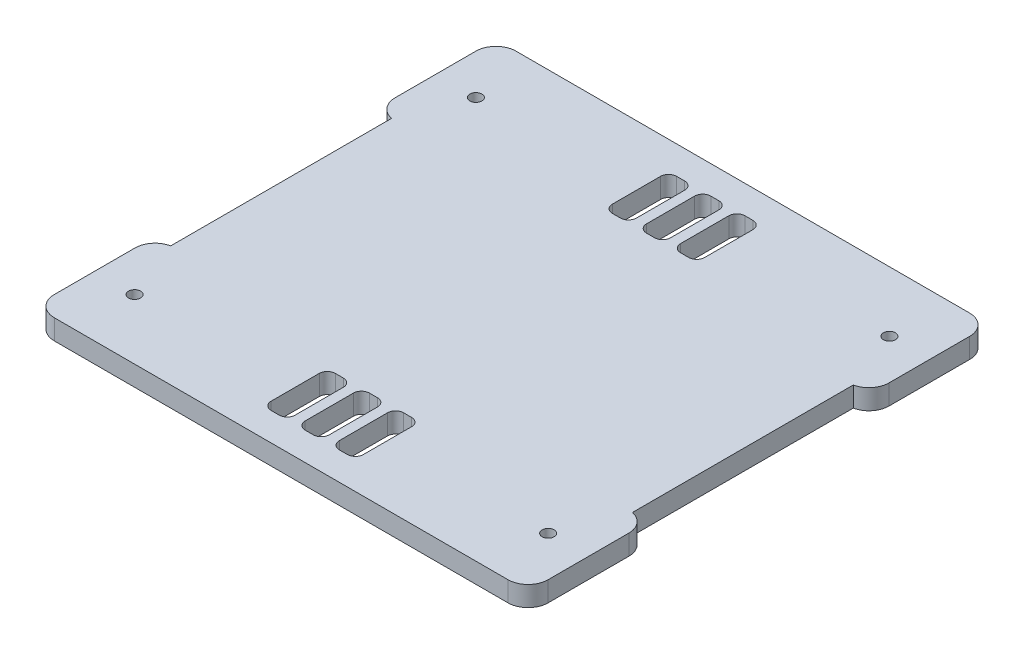
SolidWorks part; units mm, degrees
ref_plane "Plano frontal" through (0, 0, 0) normal (0, 0, 1) x (1, 0, 0)
ref_plane "Plano superior" through (0, 0, 0) normal (0, 1, 0) x (1, 0, 0)
ref_plane "Plano direito" through (0, 0, 0) normal (1, 0, 0) x (0, 0, -1)
sketch "Esboço1" plane through (0, 0, 0) normal (0, 1, 0) x (1, 0, 0)
  line L0 (81.9059, -20.4292) -> (85.9059, -20.4292)
  line L1 (-32.0941, 9.5708) -> (80.9059, 9.5708)
  line L2 (-37.0941, 4.5708) -> (-37.0941, -20.4292)
  line L3 (-37.0941, -20.4292) -> (-33.0941, -20.4292)
  line L4 (85.9059, 4.5708) -> (85.9059, -20.4292)
  line L6 (-33.0941, -20.4292) -> (-33.0941, -75.4292)
  line L8 (81.9059, -20.4292) -> (81.9059, -75.4292)
  line L9 (-37.0941, -75.4292) -> (-33.0941, -75.4292)
  line L10 (-37.0941, -75.4292) -> (-37.0941, -100.4292)
  line L11 (-32.0941, -105.4292) -> (80.9059, -105.4292)
  line L12 (85.9059, -75.4292) -> (85.9059, -100.4292)
  line L13 (81.9059, -75.4292) -> (85.9059, -75.4292)
  arc A0 (-32.0941, 9.5708) -> (-37.0941, 4.5708) centre (-32.0941, 4.5708) ccw
  arc A1 (80.9059, 9.5708) -> (85.9059, 4.5708) centre (80.9059, 4.5708) cw
  arc A2 (80.9059, -105.4292) -> (85.9059, -100.4292) centre (80.9059, -100.4292) ccw
  arc A3 (-37.0941, -100.4292) -> (-32.0941, -105.4292) centre (-32.0941, -100.4292) ccw
  point P14 (-37.0941, 9.5708)
  point P19 (85.9059, -105.4292)
  point P22 (-37.0941, -105.4292)
  dimension "D9" = 5
  dimension "D1" = 30
  dimension "D2" = 123
  dimension "D3" = 115
  dimension "D4" = 55
  dimension "D5" = 4
  dimension "D6" = 4
  dimension "D7" = 123
  dimension "D8" = 30
extrude "Ressalto-extrusão1" add sketch "Esboço1" along normal blind 5
fillet "Filete1" radius 5 4 edges at (-37.0941, 2.5, 75.4292) (-37.0941, 2.5, 20.4292) (85.9059, 2.5, 20.4292) (85.9059, 2.5, 75.4292)
sketch "Esboço3" plane through (0, 0, 0) normal (0, -1, 0) x (1, 0, 0)
  line L0 (-37.0941, -4.5708) -> (-37.0941, 15.5302) construction
  line L1 (80.9059, -9.5708) -> (-32.0941, -9.5708) construction
  line L2 (85.9059, 15.5302) -> (85.9059, -4.5708) construction
  line L3 (-33.0941, 47.9292) -> (81.9059, 47.9292) construction
  line L4 (-33.0941, 20.4292) -> (-33.0941, 75.4292) construction
  line L5 (81.9059, 75.4292) -> (81.9059, 20.4292) construction
  line L6 (35.9059, 84.4292) -> (35.9059, 96.4292)
  line L7 (14.9059, 13.4292) -> (16.9059, 13.4292)
  line L8 (12.9059, 11.4292) -> (12.9059, -0.5708)
  line L9 (14.9059, -2.5708) -> (16.9059, -2.5708)
  line L10 (18.9059, 11.4292) -> (18.9059, -0.5708)
  line L11 (23.4059, 13.4292) -> (25.4059, 13.4292)
  line L12 (21.4059, 11.4292) -> (21.4059, -0.5708)
  line L13 (23.4059, -2.5708) -> (25.4059, -2.5708)
  line L14 (27.4059, 11.4292) -> (27.4059, -0.5708)
  line L15 (31.9059, 13.4292) -> (33.9059, 13.4292)
  line L16 (29.9059, 11.4292) -> (29.9059, -0.5708)
  line L17 (31.9059, -2.5708) -> (33.9059, -2.5708)
  line L18 (35.9059, 11.4292) -> (35.9059, -0.5708)
  line L19 (31.9059, 98.4292) -> (33.9059, 98.4292)
  line L20 (29.9059, 84.4292) -> (29.9059, 96.4292)
  line L21 (31.9059, 82.4292) -> (33.9059, 82.4292)
  line L22 (27.4059, 84.4292) -> (27.4059, 96.4292)
  line L23 (23.4059, 98.4292) -> (25.4059, 98.4292)
  line L24 (21.4059, 84.4292) -> (21.4059, 96.4292)
  line L25 (23.4059, 82.4292) -> (25.4059, 82.4292)
  line L26 (18.9059, 84.4292) -> (18.9059, 96.4292)
  line L27 (14.9059, 98.4292) -> (16.9059, 98.4292)
  line L28 (12.9059, 84.4292) -> (12.9059, 96.4292)
  line L29 (14.9059, 82.4292) -> (16.9059, 82.4292)
  circle A0 centre (-27.0941, 5.4292) radius 1.5
  circle A1 centre (75.9059, 5.4292) radius 1.5
  arc A2 (31.9059, 13.4292) -> (29.9059, 11.4292) centre (31.9059, 11.4292) ccw
  arc A3 (33.9059, 13.4292) -> (35.9059, 11.4292) centre (33.9059, 11.4292) cw
  arc A4 (33.9059, -2.5708) -> (35.9059, -0.5708) centre (33.9059, -0.5708) ccw
  arc A5 (29.9059, -0.5708) -> (31.9059, -2.5708) centre (31.9059, -0.5708) ccw
  arc A6 (25.4059, -2.5708) -> (27.4059, -0.5708) centre (25.4059, -0.5708) ccw
  arc A7 (25.4059, 13.4292) -> (27.4059, 11.4292) centre (25.4059, 11.4292) cw
  arc A8 (23.4059, 13.4292) -> (21.4059, 11.4292) centre (23.4059, 11.4292) ccw
  arc A9 (21.4059, -0.5708) -> (23.4059, -2.5708) centre (23.4059, -0.5708) ccw
  arc A10 (14.9059, 13.4292) -> (12.9059, 11.4292) centre (14.9059, 11.4292) ccw
  arc A11 (16.9059, 13.4292) -> (18.9059, 11.4292) centre (16.9059, 11.4292) cw
  arc A12 (16.9059, -2.5708) -> (18.9059, -0.5708) centre (16.9059, -0.5708) ccw
  arc A13 (12.9059, -0.5708) -> (14.9059, -2.5708) centre (14.9059, -0.5708) ccw
  arc A14 (12.9059, 96.4292) -> (14.9059, 98.4292) centre (14.9059, 96.4292) cw
  arc A15 (16.9059, 98.4292) -> (18.9059, 96.4292) centre (16.9059, 96.4292) cw
  arc A16 (16.9059, 82.4292) -> (18.9059, 84.4292) centre (16.9059, 84.4292) ccw
  arc A17 (14.9059, 82.4292) -> (12.9059, 84.4292) centre (14.9059, 84.4292) cw
  arc A18 (21.4059, 96.4292) -> (23.4059, 98.4292) centre (23.4059, 96.4292) cw
  arc A19 (23.4059, 82.4292) -> (21.4059, 84.4292) centre (23.4059, 84.4292) cw
  arc A20 (25.4059, 82.4292) -> (27.4059, 84.4292) centre (25.4059, 84.4292) ccw
  arc A21 (25.4059, 98.4292) -> (27.4059, 96.4292) centre (25.4059, 96.4292) cw
  arc A22 (29.9059, 96.4292) -> (31.9059, 98.4292) centre (31.9059, 96.4292) cw
  arc A23 (33.9059, 98.4292) -> (35.9059, 96.4292) centre (33.9059, 96.4292) cw
  arc A24 (33.9059, 82.4292) -> (35.9059, 84.4292) centre (33.9059, 84.4292) ccw
  arc A25 (31.9059, 82.4292) -> (29.9059, 84.4292) centre (31.9059, 84.4292) cw
  circle A26 centre (75.9059, 90.4292) radius 1.5
  circle A27 centre (-27.0941, 90.4292) radius 1.5
  point P30 (29.9059, 13.4292)
  point P33 (35.9059, 13.4292)
  point P38 (29.9059, -2.5708)
  point P43 (27.4059, 13.4292)
  point P46 (21.4059, 13.4292)
  point P49 (21.4059, -2.5708)
  point P52 (12.9059, 13.4292)
  point P55 (18.9059, 13.4292)
  point P60 (12.9059, -2.5708)
  point P101 (12.9059, 98.4292)
  point P102 (18.9059, 82.4292)
  point P103 (12.9059, 82.4292)
  point P104 (21.4059, 98.4292)
  point P105 (21.4059, 82.4292)
  point P106 (27.4059, 82.4292)
  point P107 (29.9059, 98.4292)
  point P108 (35.9059, 82.4292)
  point P109 (29.9059, 82.4292)
  point P110 (24.4059, -9.5708)
  dimension "D1" = 10
  dimension "D2" = 15
  dimension "D3" = 3
  dimension "D4" = 10
  dimension "D5" = 15
  dimension "D6" = 3
  dimension "D18" = 2
  dimension "D7" = 2.5
  dimension "D8" = 2.5
  dimension "D9" = 6
  dimension "D10" = 6
  dimension "D11" = 6
  dimension "D12" = 50
  dimension "D13" = 50
  dimension "D14" = 16
  dimension "D15" = 16
  dimension "D16" = 16
  dimension "D17" = 7
  dimension "D19" = 7
extrude "Corte-extrusão1" cut sketch "Esboço3" against normal blind 5
